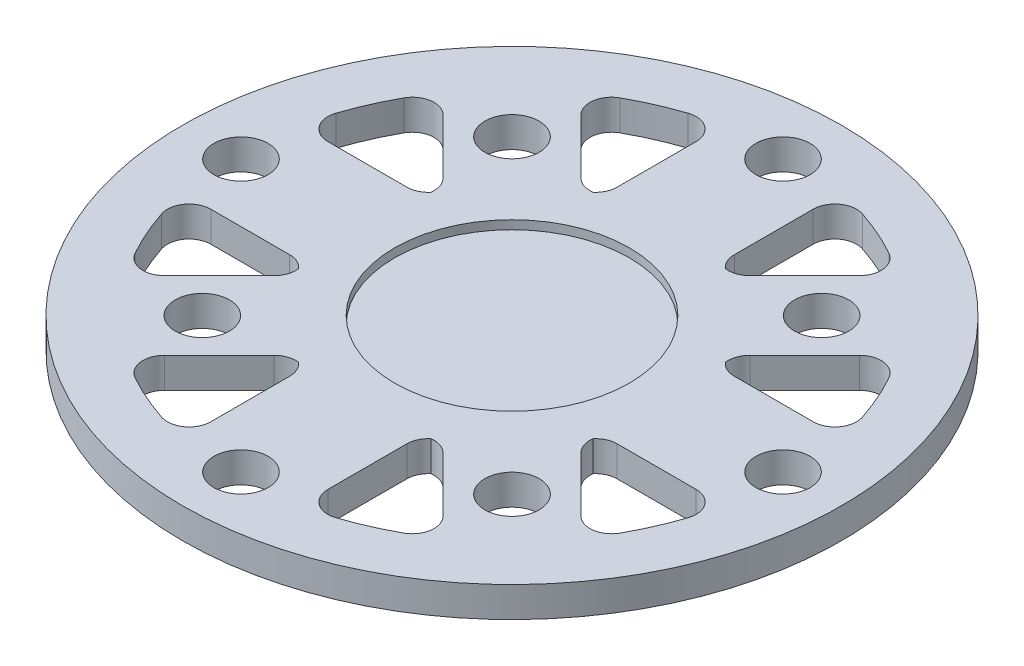
SolidWorks part; units mm, degrees
material "Custom Plastic"
ref_plane "Front Plane" through (0, 0, 0) normal (0, 0, 1) x (1, 0, 0)
ref_plane "Top Plane" through (0, 0, 0) normal (0, 1, 0) x (1, 0, 0)
ref_plane "Right Plane" through (0, 0, 0) normal (1, 0, 0) x (0, 0, -1)
sketch "Sketch1" plane through (0, 0, 0) normal (0, 1, 0) x (1, 0, 0)
  circle A0 centre (0, 0) radius 76
  circle A1 centre (0, 0) radius 27.051
  circle A2 centre (0, 0) radius 62.5 construction
  circle A3 centre (0, 62.5) radius 6.25
  circle A4 centre (62.5, 0) radius 6.25
  circle A5 centre (0, -62.5) radius 6.25
  circle A6 centre (-62.5, 0) radius 6.25
  dimension "D1" = 152
  dimension "D2" = 54.102
  dimension "D3" = 125
  dimension "D4" = 12.5
extrude "Boss-Extrude1" add sketch "Sketch1" along normal blind 7
sketch "Sketch3" plane through (0, 0, 0) normal (0, -1, 0) x (1, 0, 0)
  circle A0 centre (0, 0) radius 27.051
extrude "Boss-Extrude2" add sketch "Sketch3" against normal blind 5
sketch "Sketch4" plane through (0, 7, 0) normal (0, 1, 0) x (1, 0, 0)
  line L0 (134.0846, 0) -> (0, 0) construction
  line L1 (0, 0) -> (0, 97.8812) construction
  line L2 (13.5, 62.5) -> (13.5, 34.504)
  line L3 (34.504, 13.5) -> (62.5, 13.5)
  line L4 (-34.504, 13.5) -> (-62.5, 13.5)
  line L5 (-13.5, 62.5) -> (-13.5, 34.504)
  line L6 (34.504, -13.5) -> (62.5, -13.5)
  line L7 (13.5, -62.5) -> (13.5, -34.504)
  line L8 (-13.5, -62.5) -> (-13.5, -34.504)
  line L9 (-34.504, -13.5) -> (-62.5, -13.5)
  line L10 (26.199, 26.199) -> (45.2134, 45.2134)
  line L11 (0, 0) -> (72.917, 72.917) construction
  line L12 (36.5531, 52.463) -> (17.0072, 32.9171)
  line L13 (52.463, 36.5531) -> (32.9171, 17.0072)
  line L14 (36.5531, -52.463) -> (17.0072, -32.9171)
  line L15 (52.463, -36.5531) -> (32.9171, -17.0072)
  line L16 (-52.463, -36.5531) -> (-32.9171, -17.0072)
  line L17 (-36.5531, -52.463) -> (-17.0072, -32.9171)
  line L18 (-52.463, 36.5531) -> (-32.9171, 17.0072)
  line L19 (-36.5531, 52.463) -> (-17.0072, 32.9171)
  arc A0 (13.5, 62.5) -> (62.5, 13.5) centre (0, 0) cw
  circle A1 centre (35.7062, 35.7062) radius 6.25
  circle A2 centre (35.7062, 35.7062) radius 11.25
  circle A5 centre (35.7062, -35.7062) radius 6.25
  arc A7 (-13.5, 62.5) -> (-62.5, 13.5) centre (0, 0) ccw
  arc A8 (13.5, -62.5) -> (62.5, -13.5) centre (0, 0) ccw
  arc A10 (-13.5, -62.5) -> (-62.5, -13.5) centre (0, 0) cw
  circle A11 centre (0, 0) radius 37.051
  circle A12 centre (0, 0) radius 27.051 construction
  circle A13 centre (35.7062, -35.7062) radius 11.25
  circle A14 centre (-35.7062, -35.7062) radius 6.25
  circle A15 centre (-35.7062, -35.7062) radius 11.25
  circle A16 centre (-35.7062, 35.7062) radius 6.25
  circle A17 centre (-35.7062, 35.7062) radius 11.25
  point P18 (33.4267, 54.5083)
  dimension "D1" = 10
  dimension "D4" = 63.9414
  dimension "D6" = 12.5
  dimension "D7" = 5
  dimension "D2" = 27
  dimension "D3" = 27
  dimension "D5" = 45
extrude "Cut-Extrude1" cut sketch "Sketch4" against normal blind 10 contours A11 L7 A8 L14 | A11 L15 A8 L6 | A11 L17 A10 L8 | A11 L9 A10 L16 | A11 L18 A7 L4 | A11 L5 A7 L19 | A11 L12 A0 L2 | A11 L3 A0 L13 | A1 | A5 | A14 | A16 region at (21.5497, 7, -49.012) region at (-21.5497, 7, -49.012) region at (49.012, 7, -21.5497) region at (-49.012, 7, -21.5497) region at (-49.012, 7, 21.5497) region at (49.012, 7, 21.5497) region at (-21.5497, 7, 49.012) region at (21.5497, 7, 49.012)
fillet "Fillet1" radius 5 32 edges at (34.504, 3.5, 13.5) (62.5, 3.5, 13.5) (52.463, 3.5, 36.5531) (32.9171, 3.5, 17.0072) (32.9171, 3.5, -17.0072) (34.504, 3.5, -13.5) (62.5, 3.5, -13.5) (52.463, 3.5, -36.5531) (36.5531, 3.5, -52.463) (13.5, 3.5, -62.5) (13.5, 3.5, -34.504) (17.0072, 3.5, -32.9171) (-17.0072, 3.5, -32.9171) (-36.5531, 3.5, -52.463) (-13.5, 3.5, -34.504) (-13.5, 3.5, -62.5) (-32.9171, 3.5, -17.0072) (-52.463, 3.5, -36.5531) (-62.5, 3.5, -13.5) (-34.504, 3.5, -13.5) (-32.9171, 3.5, 17.0072) (-34.504, 3.5, 13.5) (-62.5, 3.5, 13.5) (-52.463, 3.5, 36.5531) (-36.5531, 3.5, 52.463) (-13.5, 3.5, 62.5) (-13.5, 3.5, 34.504) (-17.0072, 3.5, 32.9171) (17.0072, 3.5, 32.9171) (13.5, 3.5, 34.504) (13.5, 3.5, 62.5) (36.5531, 3.5, 52.463)
